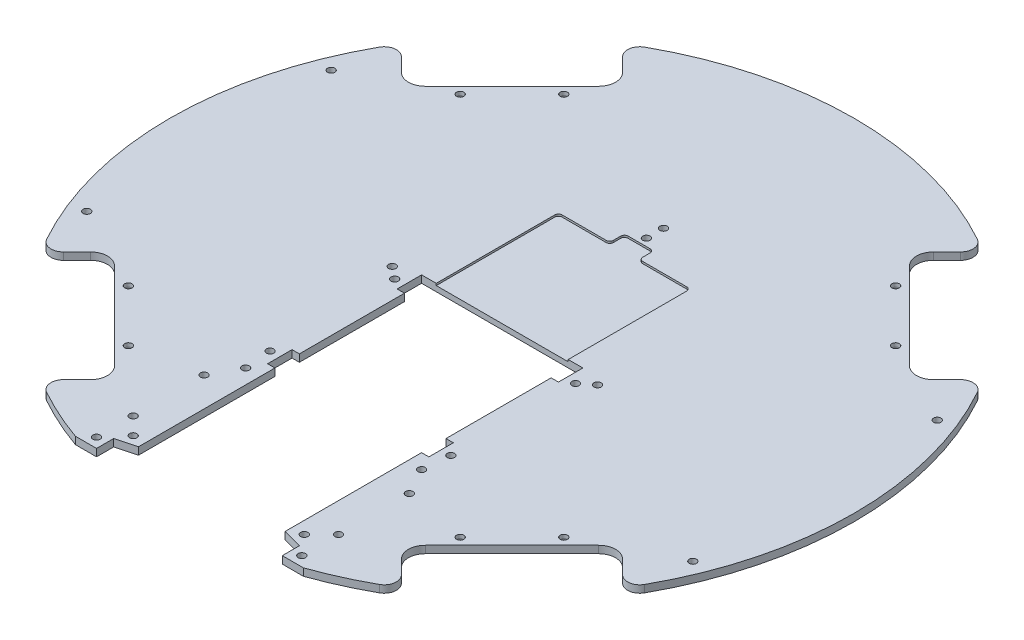
SolidWorks part; units mm, degrees
material "1060 Alloy"
ref_plane "Front Plane" through (0, 0, 0) normal (0, 0, 1) x (1, 0, 0)
ref_plane "Top Plane" through (0, 0, 0) normal (0, 1, 0) x (1, 0, 0)
ref_plane "Right Plane" through (0, 0, 0) normal (1, 0, 0) x (0, 0, -1)
sketch "Sketch1" plane through (0, 0, 0) normal (0, 1, 0) x (1, 0, 0)
  circle A0 centre (0, 0) radius 140
  dimension "D1" = 280
extrude "Boss-Extrude1" add sketch "Sketch1" along normal blind 3
sketch "Sketch7" plane through (0, 3, 0) normal (0, 1, 0) x (1, 0, 0)
  line L0 (-99.0303, -63.6043) -> (-63.6043, -99.0303)
  line L1 (-108.8591, -63.6043) -> (-121.6224, -76.3675)
  line L2 (-63.6043, -108.8591) -> (-76.3675, -121.6224)
  line L3 (-121.6224, -76.3675) -> (-76.3675, -121.6224)
  line L4 (0, 0) -> (-98.9949, -98.9949) construction
  line L7 (0, 0) -> (0, 130) construction
  circle A0 centre (0, 0) radius 140 construction
  arc A1 (-108.8591, -63.6043) -> (-99.0303, -63.6043) centre (-103.9447, -68.5186) cw
  arc A2 (-63.6043, -99.0303) -> (-63.6043, -108.8591) centre (-68.5186, -103.9447) cw
  dimension "D4" = 6.95
  dimension "D1" = 115
  dimension "D2" = 64
  dimension "D3" = 135
extrude "Cut-Extrude4" cut sketch "Sketch7" against normal up to next
sketch "Sketch9" plane through (0, 3, 0) normal (0, 1, 0) x (1, 0, 0)
  line L1 (-63.6043, -99.0303) -> (-99.0303, -63.6043) construction
  line L4 (-108.8591, -63.6043) -> (-119.0017, -73.7469) construction
  circle A0 centre (-89.0955, -67.8823) radius 1.5
  circle A1 centre (-67.8823, -89.0955) radius 1.5
  dimension "D4" = 3
  dimension "D1" = 4
  dimension "D2" = 30
  dimension "D3" = 17
  dimension "D5" = 4
extrude "Cut-Extrude6" cut sketch "Sketch9" against normal up to next
fillet "Fillet1" radius 5 2 edges at (-73.7469, 1.5, 119.0017) (-119.0017, 1.5, 73.7469)
pattern_circular "CirPattern1" count 4 over 360 about axis through (0, 3, 0) along (0, 1, 0) of "Cut-Extrude4", "Fillet1", "Cut-Extrude6"
sketch "Sketch2" plane through (0, 3, 0) normal (0, 1, 0) x (1, 0, 0)
  line L0 (-46.6476, -132) -> (-38, -132)
  line L1 (-30, -122.8564) -> (-30, -67)
  line L2 (-33, -4) -> (33, -4)
  line L3 (30, -67) -> (30, -122.8564)
  line L4 (38, -132) -> (46.6476, -132)
  line L5 (46.6476, -132) -> (46.6476, -140)
  line L6 (46.6476, -140) -> (-46.6476, -140)
  line L7 (-46.6476, -140) -> (-46.6476, -132)
  line L8 (-33, -57) -> (-33, -67)
  line L9 (-33, -67) -> (-30, -67)
  line L10 (33, -57) -> (33, -67)
  line L11 (33, -67) -> (30, -67)
  line L12 (-33, -57) -> (-30, -57)
  line L13 (-30, -57) -> (-30, -14)
  line L14 (-30, -14) -> (-33, -14)
  line L15 (-33, -14) -> (-33, -4)
  line L16 (33, -4) -> (33, -14)
  line L17 (33, -14) -> (30, -14)
  line L18 (30, -14) -> (30, -57)
  line L19 (30, -57) -> (33, -57)
  line L20 (-38, -132) -> (-38, -125)
  line L21 (-38, -125) -> (-30, -122.8564)
  line L22 (38, -132) -> (38, -125)
  line L23 (38, -125) -> (30, -122.8564)
  circle A0 centre (0, 0) radius 140 construction
  dimension "D8" = 3
  dimension "D5" = 63
  dimension "D6" = 66
  dimension "D1" = 8
  dimension "D2" = 65
  dimension "D3" = 60
  dimension "D4" = 16.6476
  dimension "D7" = 10
  dimension "D9" = 76
  dimension "D10" = 7
  dimension "D11" = 105
extrude "Cut-Extrude1" cut sketch "Sketch2" against normal up to next
fillet "Fillet3" radius 1.5 8 edges at (67.8823, 0, 90.5955) (89.0955, 0, 69.3823) (89.0955, 0, -66.3823) (67.8823, 0, -87.5955) (-67.8823, 0, -87.5955) (-89.0955, 0, -66.3823) (-67.8823, 0, 90.5955) (-89.0955, 0, 69.3823)
sketch "Sketch10" plane through (0, 3, 0) normal (0, 1, 0) x (1, 0, 0)
  line L0 (-33, -57) -> (-33, -67) construction
  line L1 (33, -67) -> (33, -57) construction
  line L2 (-33, -67) -> (-30, -67) construction
  line L4 (-30, -14) -> (-33, -14) construction
  line L5 (33, -4) -> (-33, -4) construction
  circle A0 centre (-37, -62) radius 1.5
  circle A1 centre (37, -62) radius 1.5
  circle A2 centre (-37, -11) radius 1.5
  circle A3 centre (37, -11) radius 1.5
  circle A4 centre (-42, -7) radius 1.5
  circle A5 centre (42, -7) radius 1.5
  point P17 (-31.5, -14)
  dimension "D3" = 3
  dimension "D1" = 4
  dimension "D2" = 4
  dimension "D4" = 5
  dimension "D5" = 3
  dimension "D6" = 3
  dimension "D7" = 5
  dimension "D8" = 5
extrude "Cut-Extrude7" cut sketch "Sketch10" against normal up to next
sketch "Sketch13" plane through (0, 3, 0) normal (0, 1, 0) x (1, 0, 0)
  line L0 (-38, -132) -> (-46.6476, -132) construction
  line L1 (-38, -132) -> (-46.6476, -132) construction
  circle A0 centre (-42, -84) radius 1.5
  circle A1 centre (-42, -113) radius 1.5
  circle A2 centre (42, -113) radius 1.5
  circle A3 centre (42, -84) radius 1.5
  dimension "D1" = 3
  dimension "D2" = 19
  dimension "D3" = 48
  dimension "D4" = 42
  dimension "D5" = 42
extrude "Cut-Extrude9" cut sketch "Sketch13" against normal up to next
sketch "Sketch16" plane through (0, 3, 0) normal (0, 1, 0) x (1, 0, 0)
  circle A0 centre (0, 62) radius 1.5
  circle A4 centre (0, 55) radius 1.5
  dimension "D2" = 3
  dimension "D5" = 3
  dimension "D1" = 62
  dimension "D7" = 55
extrude "Cut-Extrude12" cut sketch "Sketch16" against normal up to next
sketch "Sketch17" plane through (0, 3, 0) normal (0, 1, 0) x (1, 0, 0)
  circle A0 centre (-124, 50) radius 1.5
  circle A1 centre (-124, -50) radius 1.5
  circle A2 centre (124, 50) radius 1.5
  circle A3 centre (124, -50) radius 1.5
  dimension "D1" = 3
  dimension "D2" = 50
  dimension "D3" = 50
  dimension "D4" = 124
  dimension "D5" = 124
extrude "Cut-Extrude13" cut sketch "Sketch17" against normal up to next
sketch "Sketch18" plane through (0, 3, 0) normal (0, 1, 0) x (1, 0, 0)
  line L1 (-27, -4) -> (27, -4)
  line L2 (-27, -4) -> (-27, 46)
  line L3 (-27, 46) -> (27, 46)
  line L4 (27, -4) -> (27, 46)
  line L5 (33, -4) -> (-33, -4) construction
  dimension "D1" = 50
  dimension "D2" = 54
  dimension "D3" = 27
extrude "Cut-Extrude14" cut sketch "Sketch18" against normal blind 0.8
sketch "Sketch19" plane through (0, 3, 0) normal (0, 1, 0) x (1, 0, 0)
  line L0 (-38, -125) -> (-38, -132) construction
  line L1 (-38, -132) -> (-46.6476, -132) construction
  line L2 (38, -132) -> (38, -125) construction
  circle A0 centre (-42, -128) radius 1.5
  circle A1 centre (42, -128) radius 1.5
  dimension "D4" = 3
  dimension "D1" = 4
  dimension "D2" = 4
  dimension "D3" = 4
extrude "Cut-Extrude15" cut sketch "Sketch19" against normal up to next
sketch "Sketch20" plane through (0, 3, 0) normal (0, 1, 0) x (1, 0, 0)
  line L0 (27, 46) -> (-27, 46) construction
  line L1 (-6, 46) -> (6, 46)
  line L2 (-6, 46) -> (-6, 52)
  line L3 (-6, 52) -> (6, 52)
  line L4 (6, 46) -> (6, 52)
  circle A0 centre (0, 55) radius 1.5 construction
  dimension "D1" = 12
  dimension "D2" = 6
  dimension "D3" = 3
extrude "Cut-Extrude16" cut sketch "Sketch20" against normal up to surface (0.8 mm away) up to face at (0, 2.2, -21)
fillet "Fillet4" radius 1.5 6 edges at (6, 2.6, -46) (27, 2.6, -46) (-27, 2.6, -46) (-6, 2.6, -46) (6, 2.6, -52) (-6, 2.6, -52)
sketch "Sketch21" plane through (0, 3, 0) normal (0, 1, 0) x (1, 0, 0)
  circle A0 centre (-35, -120) radius 1.5
  circle A1 centre (-36, -73) radius 1.5
  circle A2 centre (35, -120) radius 1.5
  circle A3 centre (36, -73) radius 1.5
  circle A4 centre (-42, -128) radius 1.5 construction
  circle A5 centre (42, -128) radius 1.5 construction
  dimension "D1" = 7
  dimension "D3" = 3
  dimension "D2" = 8
  dimension "D4" = 47
  dimension "D5" = 1
  dimension "D6" = 1
  dimension "D7" = 7
extrude "Cut-Extrude17" cut sketch "Sketch21" against normal up to next
